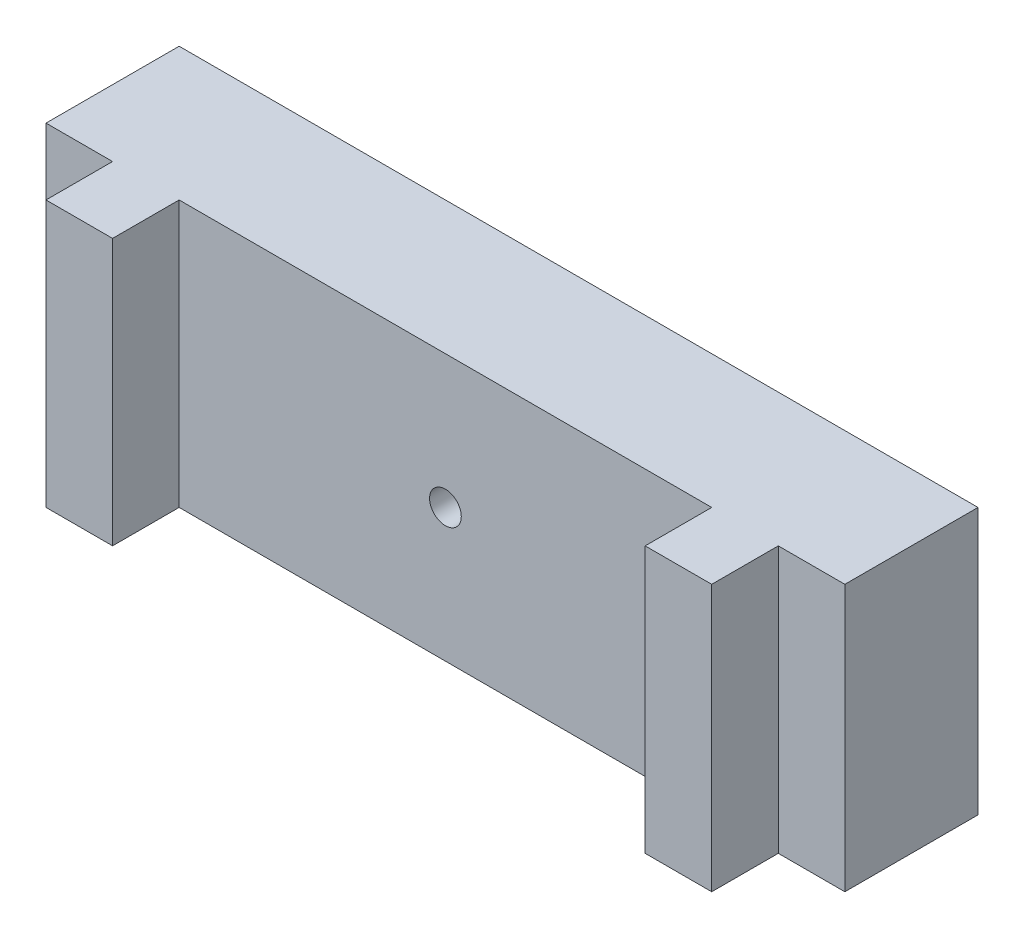
SolidWorks part; units mm, degrees
ref_plane "Front Plane" through (0, 0, 0) normal (0, 0, 1) x (1, 0, 0)
ref_plane "Top Plane" through (0, 0, 0) normal (0, 1, 0) x (1, 0, 0)
ref_plane "Right Plane" through (0, 0, 0) normal (1, 0, 0) x (0, 0, -1)
sketch "Sketch1" plane through (0, 0, 0) normal (0, 0, 1) x (1, 0, 0)
  line L1 (-38.1, -12.7) -> (38.1, -12.7)
  line L2 (-38.1, -12.7) -> (-38.1, 12.7)
  line L3 (-38.1, 12.7) -> (38.1, 12.7)
  line L4 (38.1, -12.7) -> (38.1, 12.7)
  line L5 (-38.1, -12.7) -> (38.1, 12.7) construction
  line L6 (-38.1, 12.7) -> (38.1, -12.7) construction
  point P0 (0, 0)
  dimension "D1" = 76.2
  dimension "D2" = 25.4
extrude "Boss-Extrude1" add sketch "Sketch1" along normal blind 6.35 and the other way blind 6.35
sketch "Sketch4" plane through (0, 0, 6.35) normal (0, 0, 1) x (1, 0, 0)
  line L5 (38.1, 12.7) -> (-38.1, 12.7) construction
  line L6 (-31.75, -12.7) -> (-25.4, -12.7)
  line L7 (-38.1, 0) -> (38.1, 0) construction
  line L8 (-38.1, 12.7) -> (-38.1, -12.7) construction
  line L9 (38.1, -12.7) -> (38.1, 12.7) construction
  line L10 (-31.75, -12.7) -> (-31.75, 12.7)
  line L11 (-31.75, 12.7) -> (-25.4, 12.7)
  line L12 (-25.4, -12.7) -> (-25.4, 12.7)
  line L13 (-31.75, -12.7) -> (-25.4, 12.7) construction
  line L14 (-31.75, 12.7) -> (-25.4, -12.7) construction
  line L15 (25.4, -12.7) -> (31.75, -12.7)
  line L16 (25.4, -12.7) -> (25.4, 12.7)
  line L17 (25.4, 12.7) -> (31.75, 12.7)
  line L18 (31.75, -12.7) -> (31.75, 12.7)
  line L19 (-38.1, -12.7) -> (38.1, -12.7) construction
  point P0 (-28.575, 0)
  point P13 (0, 0)
  dimension "D1" = 6.35
  dimension "D2" = 6.35
  dimension "D3" = 6.35
  dimension "D4" = 6.35
extrude "Boss-Extrude3" add sketch "Sketch4" along normal blind 6.35
sketch "Sketch6" plane through (0, 0, 6.35) normal (0, 0, 1) x (1, 0, 0)
  circle A0 centre (0, 0) radius 1.5113
extrude "Cut-Extrude1" cut sketch "Sketch6" against normal through all
